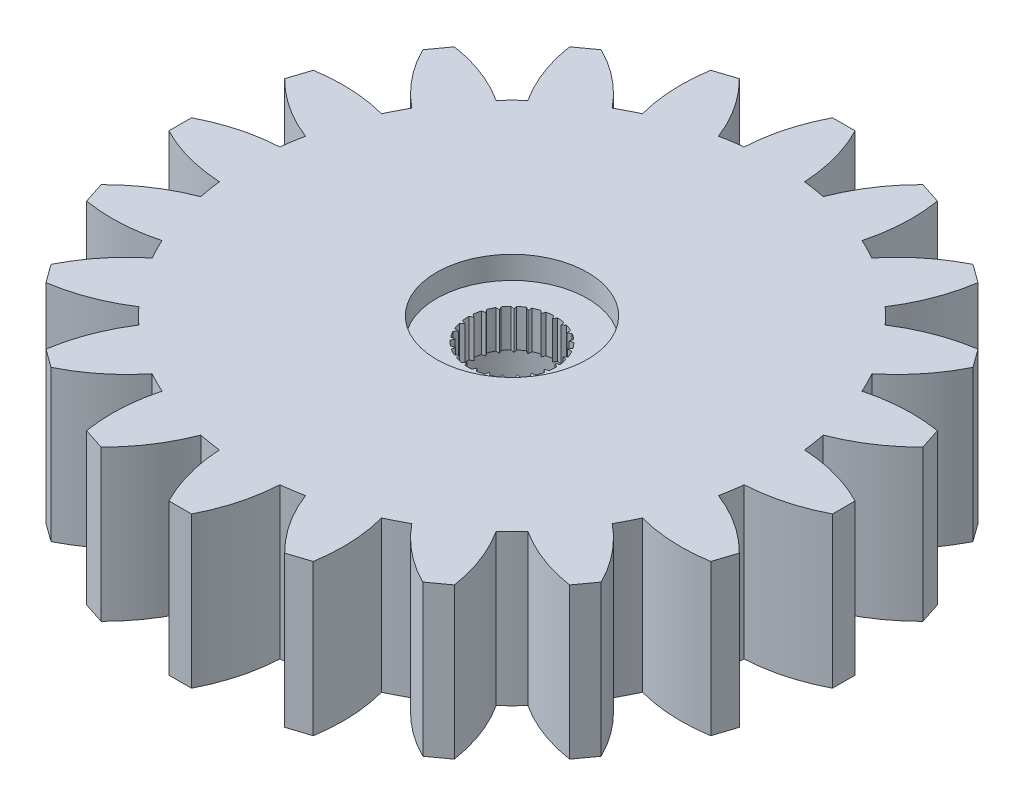
SolidWorks part; units mm, degrees
ref_plane "Front Plane" through (0, 0, 0) normal (0, 0, 1) x (1, 0, 0)
ref_plane "Top Plane" through (0, 0, 0) normal (0, 1, 0) x (1, 0, 0)
ref_plane "Right Plane" through (0, 0, 0) normal (1, 0, 0) x (0, 0, -1)
sketch "Sketch2" plane through (0, 0, 0) normal (0, 1, 0) x (1, 0, 0)
  line L0 (0, -10.2886) -> (0, 10.2886) construction
  line L1 (0, 0) -> (0.6267, 4.1579) construction
  line L2 (0, 0) -> (-0.6267, 4.1579) construction
  line L3 (0, 0) -> (1.373, 17.4461) construction
  line L4 (0, 0) -> (-1.373, 17.4461) construction
  line L5 (-0.1283, 2.8972) -> (0, 2.675)
  line L6 (0, 2.675) -> (0.1283, 2.8972)
  line L7 (-0.75, 21.9872) -> (0.75, 21.9872)
  line L8 (0.6652, 2.591) -> (0.8447, 2.7742)
  line L9 (7.8676, 46.3212) -> (7.9539, 46.8293)
  line L10 (3.8992, 46.8226) -> (3.9419, 47.3362)
  line L11 (0.5963, 2.838) -> (0.6652, 2.591)
  line L12 (13.6112, 44.9699) -> (13.7605, 45.4632)
  line L13 (9.7368, 45.9647) -> (9.8436, 46.4688)
  line L14 (1.2887, 2.3441) -> (1.5081, 2.477)
  line L15 (19.1401, 42.9094) -> (19.35, 43.38)
  line L16 (15.421, 44.3819) -> (15.5901, 44.8687)
  line L17 (1.2833, 2.6006) -> (1.2887, 2.3441)
  line L18 (24.3671, 40.1721) -> (24.6344, 40.6128)
  line L19 (20.8619, 42.0991) -> (21.0907, 42.5609)
  line L20 (1.8312, 1.95) -> (2.0767, 2.0241)
  line L21 (29.2099, 36.8013) -> (29.5303, 37.205)
  line L22 (25.9738, 39.1525) -> (26.2587, 39.5819)
  line L23 (1.8897, 2.1997) -> (1.8312, 1.95)
  line L24 (33.592, 32.8502) -> (33.9604, 33.2105)
  line L25 (30.6761, 35.5884) -> (31.0126, 35.9787)
  line L26 (2.2586, 1.4333) -> (2.5149, 1.4441)
  line L27 (37.4443, 28.381) -> (37.855, 28.6923)
  line L28 (34.8946, 31.463) -> (35.2774, 31.8081)
  line L29 (2.3774, 1.6607) -> (2.2586, 1.4333)
  line L30 (40.7061, 23.4641) -> (41.1526, 23.7215)
  line L31 (38.5628, 26.8415) -> (38.9858, 27.1359)
  line L32 (2.5441, 0.8266) -> (2.795, 0.7733)
  line L33 (43.326, 18.1773) -> (43.8012, 18.3767)
  line L34 (41.6229, 21.7966) -> (42.0794, 22.0357)
  line L35 (2.7157, 1.0173) -> (2.5441, 0.8266)
  line L36 (45.2626, 12.6038) -> (45.7591, 12.742)
  line L37 (44.0265, 16.408) -> (44.5094, 16.588)
  line L38 (2.6697, 0.168) -> (2.8995, 0.0539)
  line L39 (46.4853, 6.8315) -> (46.9952, 6.9064)
  line L40 (45.7358, 10.7606) -> (46.2375, 10.8787)
  line L41 (2.8834, 0.3099) -> (2.6697, 0.168)
  line L42 (46.975, 0.9515) -> (47.4903, 0.9619)
  line L43 (46.7238, 4.9436) -> (47.2363, 4.9978)
  line L44 (2.6276, -0.5012) -> (2.8218, -0.6689)
  line L45 (46.7238, -4.9436) -> (47.2363, -4.9978)
  line L46 (46.975, -0.9515) -> (47.4903, -0.9619)
  line L47 (2.8699, -0.4169) -> (2.6276, -0.5012)
  line L48 (45.7358, -10.7606) -> (46.2375, -10.8787)
  line L49 (46.4853, -6.8315) -> (46.9952, -6.9064)
  line L50 (2.4204, -1.139) -> (2.5668, -1.3496)
  line L51 (44.0265, -16.408) -> (44.5094, -16.588)
  line L52 (45.2626, -12.6038) -> (45.7591, -12.742)
  line L53 (2.676, -1.1175) -> (2.4204, -1.139)
  line L54 (41.6229, -21.7966) -> (42.0794, -22.0357)
  line L55 (43.326, -18.1773) -> (43.8012, -18.3767)
  line L56 (2.0611, -1.7051) -> (2.1505, -1.9456)
  line L57 (38.5628, -26.8415) -> (38.9858, -27.1359)
  line L58 (40.7061, -23.4641) -> (41.1526, -23.7215)
  line L59 (2.3141, -1.7479) -> (2.0611, -1.7051)
  line L60 (34.8946, -31.463) -> (35.2774, -31.8081)
  line L61 (37.4443, -28.381) -> (37.855, -28.6923)
  line L62 (1.5723, -2.1641) -> (1.5991, -2.4192)
  line L63 (30.6761, -35.5884) -> (31.0126, -35.9787)
  line L64 (33.592, -32.8502) -> (33.9604, -33.2105)
  line L65 (1.8067, -2.2685) -> (1.5723, -2.1641)
  line L66 (25.9738, -39.1525) -> (26.2587, -39.5819)
  line L67 (29.2099, -36.8013) -> (29.5303, -37.205)
  line L68 (0.9847, -2.4872) -> (0.9473, -2.7409)
  line L69 (20.8619, -42.0991) -> (21.0907, -42.5609)
  line L70 (24.3671, -40.1721) -> (24.6344, -40.6128)
  line L71 (1.1858, -2.6465) -> (0.9847, -2.4872)
  line L72 (15.421, -44.3819) -> (15.5901, -44.8687)
  line L73 (19.1401, -42.9094) -> (19.35, -43.38)
  line L74 (0.3353, -2.6539) -> (0.2359, -2.8904)
  line L75 (9.7368, -45.9647) -> (9.8436, -46.4688)
  line L76 (13.6112, -44.9699) -> (13.7605, -45.4632)
  line L77 (0.4904, -2.8582) -> (0.3353, -2.6539)
  line L78 (3.8992, -46.8226) -> (3.9419, -47.3362)
  line L79 (7.8676, -46.3212) -> (7.9539, -46.8293)
  line L80 (-0.3353, -2.6539) -> (-0.4904, -2.8582)
  line L81 (-2, -46.942) -> (-2.0219, -47.4569)
  line L82 (2, -46.942) -> (2.0219, -47.4569)
  line L83 (-0.2359, -2.8904) -> (-0.3353, -2.6539)
  line L84 (-7.8676, -46.3212) -> (-7.9539, -46.8293)
  line L85 (-3.8992, -46.8226) -> (-3.9419, -47.3362)
  line L86 (-0.9847, -2.4872) -> (-1.1858, -2.6465)
  line L87 (-13.6112, -44.9699) -> (-13.7605, -45.4632)
  line L88 (-9.7368, -45.9647) -> (-9.8436, -46.4688)
  line L89 (-0.9473, -2.7409) -> (-0.9847, -2.4872)
  line L90 (-19.1401, -42.9094) -> (-19.35, -43.38)
  line L91 (-15.421, -44.3819) -> (-15.5901, -44.8687)
  line L92 (-1.5723, -2.1641) -> (-1.8067, -2.2685)
  line L93 (-24.3671, -40.1721) -> (-24.6344, -40.6128)
  line L94 (-20.8619, -42.0991) -> (-21.0907, -42.5609)
  line L95 (-1.5991, -2.4192) -> (-1.5723, -2.1641)
  line L96 (-29.2099, -36.8013) -> (-29.5303, -37.205)
  line L97 (-25.9738, -39.1525) -> (-26.2587, -39.5819)
  line L98 (-2.0611, -1.7051) -> (-2.3141, -1.7479)
  line L99 (-33.592, -32.8502) -> (-33.9604, -33.2105)
  line L100 (-30.6761, -35.5884) -> (-31.0126, -35.9787)
  line L101 (-2.1505, -1.9456) -> (-2.0611, -1.7051)
  line L102 (-37.4443, -28.381) -> (-37.855, -28.6923)
  line L103 (-34.8946, -31.463) -> (-35.2774, -31.8081)
  line L104 (-2.4204, -1.139) -> (-2.676, -1.1175)
  line L105 (-40.7061, -23.4641) -> (-41.1526, -23.7215)
  line L106 (-38.5628, -26.8415) -> (-38.9858, -27.1359)
  line L107 (-2.5668, -1.3496) -> (-2.4204, -1.139)
  line L108 (-43.326, -18.1773) -> (-43.8012, -18.3767)
  line L109 (-41.6229, -21.7966) -> (-42.0794, -22.0357)
  line L110 (-2.6276, -0.5012) -> (-2.8699, -0.4169)
  line L111 (-45.2626, -12.6038) -> (-45.7591, -12.742)
  line L112 (-44.0265, -16.408) -> (-44.5094, -16.588)
  line L113 (-2.8218, -0.6689) -> (-2.6276, -0.5012)
  line L114 (-46.4853, -6.8315) -> (-46.9952, -6.9064)
  line L115 (-45.7358, -10.7606) -> (-46.2375, -10.8787)
  line L116 (-2.6697, 0.168) -> (-2.8834, 0.3099)
  line L117 (-46.975, -0.9515) -> (-47.4903, -0.9619)
  line L118 (-46.7238, -4.9436) -> (-47.2363, -4.9978)
  line L119 (-2.8995, 0.0539) -> (-2.6697, 0.168)
  line L120 (-46.7238, 4.9436) -> (-47.2363, 4.9978)
  line L121 (-46.975, 0.9515) -> (-47.4903, 0.9619)
  line L122 (-2.5441, 0.8266) -> (-2.7157, 1.0173)
  line L123 (-45.7358, 10.7606) -> (-46.2375, 10.8787)
  line L124 (-46.4853, 6.8315) -> (-46.9952, 6.9064)
  line L125 (-2.795, 0.7733) -> (-2.5441, 0.8266)
  line L126 (-44.0265, 16.408) -> (-44.5094, 16.588)
  line L127 (-45.2626, 12.6038) -> (-45.7591, 12.742)
  line L128 (-2.2586, 1.4333) -> (-2.3774, 1.6607)
  line L129 (-41.6229, 21.7966) -> (-42.0794, 22.0357)
  line L130 (-43.326, 18.1773) -> (-43.8012, 18.3767)
  line L131 (-2.5149, 1.4441) -> (-2.2586, 1.4333)
  line L132 (-38.5628, 26.8415) -> (-38.9858, 27.1359)
  line L133 (-40.7061, 23.4641) -> (-41.1526, 23.7215)
  line L134 (-1.8312, 1.95) -> (-1.8897, 2.1997)
  line L135 (-34.8946, 31.463) -> (-35.2774, 31.8081)
  line L136 (-37.4443, 28.381) -> (-37.855, 28.6923)
  line L137 (-2.0767, 2.0241) -> (-1.8312, 1.95)
  line L138 (-30.6761, 35.5884) -> (-31.0126, 35.9787)
  line L139 (-33.592, 32.8502) -> (-33.9604, 33.2105)
  line L140 (-1.2887, 2.3441) -> (-1.2833, 2.6006)
  line L141 (-25.9738, 39.1525) -> (-26.2587, 39.5819)
  line L142 (-29.2099, 36.8013) -> (-29.5303, 37.205)
  line L143 (-1.5081, 2.477) -> (-1.2887, 2.3441)
  line L144 (-20.8619, 42.0991) -> (-21.0907, 42.5609)
  line L145 (-24.3671, 40.1721) -> (-24.6344, 40.6128)
  line L146 (-0.6652, 2.591) -> (-0.5963, 2.838)
  line L147 (-15.421, 44.3819) -> (-15.5901, 44.8687)
  line L148 (-19.1401, 42.9094) -> (-19.35, 43.38)
  line L149 (-0.8447, 2.7742) -> (-0.6652, 2.591)
  line L150 (-9.7368, 45.9647) -> (-9.8436, 46.4688)
  line L151 (-13.6112, 44.9699) -> (-13.7605, 45.4632)
  line L153 (-3.8992, 46.8226) -> (-3.9419, 47.3362)
  line L154 (-7.8676, 46.3212) -> (-7.9539, 46.8293)
  circle A0 centre (0, 0) radius 18.7939 construction
  circle A1 centre (0, 0) radius 2.675 construction
  circle A2 centre (0, 0) radius 2.9
  circle A24 centre (0, 0) radius 17.5
  circle A25 centre (0, 0) radius 20 construction
  circle A26 centre (0, 0) radius 22 construction
  arc A27 (0.75, 21.9872) -> (2, 17.3853) centre (-9.2545, 16.799) cw
  arc A28 (-0.75, 21.9872) -> (-2, 17.3853) centre (9.2545, 16.799) ccw
  point P7 (0, 0)
  point P30 (1.5692, 19.9383)
  point P78 (0, 0)
  point P139 (0, 0)
  point P226 (0, 0)
  dimension "D1" = 5.35
  dimension "D3" = 5.8
  dimension "D5" = 37.5877
  dimension "D6" = 35
  dimension "D7" = 40
  dimension "D8" = 44
  dimension "D2" = 8.571
  dimension "D9" = 4.5
  dimension "D11" = 1.5
  dimension "D12" = 4
  dimension "D4" = 60
  dimension "D10" = 30
  dimension "D13" = 25
extrude "Boss-Extrude1" add sketch "Sketch2" along normal blind 10 contours A24 | A2 region at (0, 0, -17.005)
extrude "Boss-Extrude2" add sketch "Sketch2<4>" along normal up to surface (10 mm away) contours L7 A28 A24 A27 region at (0, 0, -19.4231) up to face at (0, 10, 17.5)
sketch "Sketch2<4>" plane through (0, 0, 0) normal (0, 1, 0) x (1, 0, 0) same geometry as "Sketch2"
pattern_circular "CirPattern1" count 20 over 360 about axis through (0, 10, 0) along (0, 1, 0) of "Boss-Extrude2"
extrude "Cut-Extrude2" cut sketch "Sketch2<7>" against normal blind 4 from surface contours L77 A2 L68 L71 L62 L65 L56 L59 L50 L53 L44 L47 L38 L41 L32 L35 L26 L29 L20 L23 L14 L17 L8 L11 L6 L5 L146 L149 L140 L143 L134 L137 L128 L131 L122 region at (0, 0, 0) starting at face at (0, 10, 0)
sketch "Sketch2<7>" plane through (0, 0, 0) normal (0, 1, 0) x (1, 0, 0) same geometry as "Sketch2"
sketch "Sketch3" plane through (0, 0, 0) normal (0, -1, 0) x (1, 0, 0)
  circle A0 centre (0, 0) radius 5
  dimension "D1" = 10
extrude "Cut-Extrude3" cut sketch "Sketch3" against normal up to surface (6 mm away) up to face at (0, 6, 0)
sketch "Sketch4" plane through (0, 10, 0) normal (0, 1, 0) x (1, 0, 0)
  circle A0 centre (0, 0) radius 5
  dimension "D1" = 10
extrude "Cut-Extrude4" cut sketch "Sketch4" against normal blind 1.5
equation "\"Module\"= 2"
equation "\"Teeth\"= 20"
equation "\"Pitch Diameter\"= \"Module\" * \"Teeth\""
equation "\"Outer Diamter\"= \"Pitch Diameter\" + ( 2 * \"Module\" )"
equation "\"Root Diameter\"= \"Pitch Diameter\" - ( 2.5 * \"Module\" )"
equation "\"Base Diamter\"= \"Pitch Diameter\" * cos ( 20 )"
equation "\"D5@Sketch2\"=\"Base Diamter\""
equation "\"D6@Sketch2\"=\"Root Diameter\""
equation "\"D8@Sketch2\"=\"Outer Diamter\""
equation "\"D9@Sketch2\"=90 / \"Teeth\""
equation "\"D7@Sketch2\"=\"Pitch Diameter\""
equation "\"D1@CirPattern1\"=\"Teeth\""
